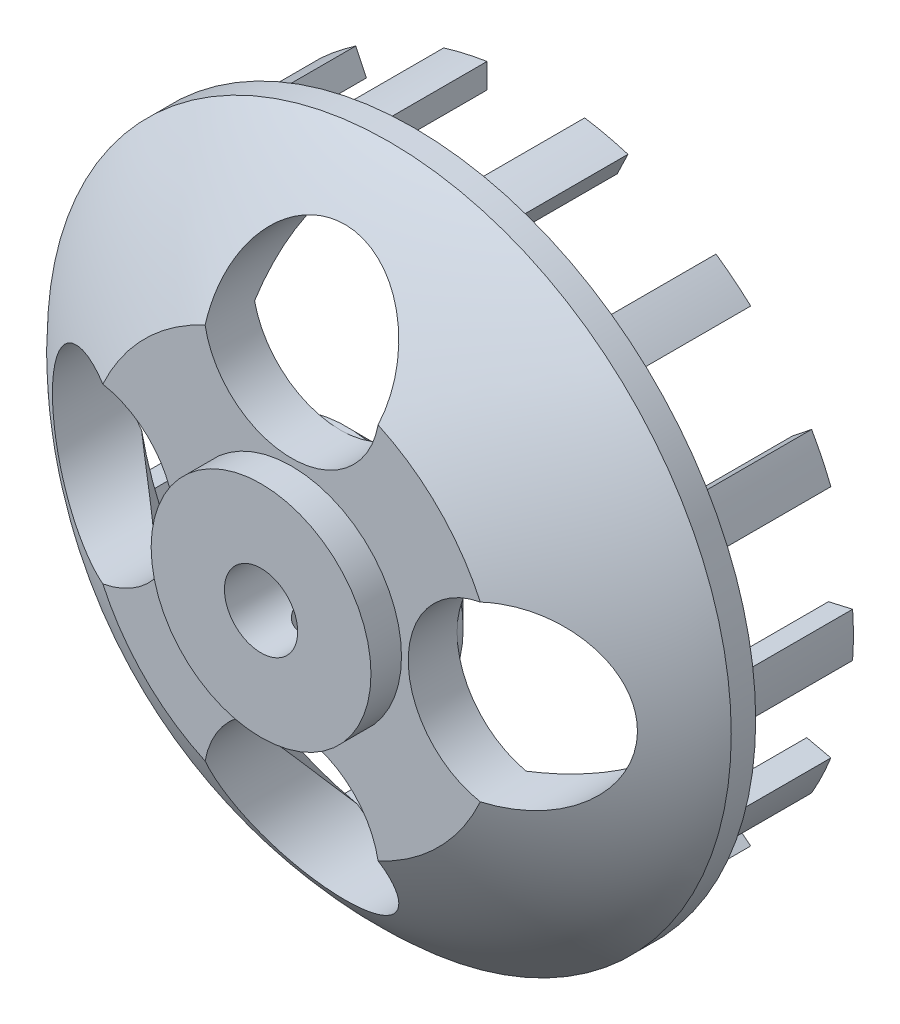
SolidWorks part; units mm, degrees
material "1060 Alloy"
ref_plane "Front Plane" through (0, 0, 0) normal (0, 0, 1) x (1, 0, 0)
ref_plane "Top Plane" through (0, 0, 0) normal (0, 1, 0) x (1, 0, 0)
ref_plane "Right Plane" through (0, 0, 0) normal (1, 0, 0) x (0, 0, -1)
sketch "Sketch1" plane through (0, 0, 0) normal (0, 0, 1) x (1, 0, 0)
  circle A0 centre (0, 0) radius 14
extrude "Boss-Extrude1" add sketch "Sketch1" along normal blind 22
sketch "Sketch2" plane through (0, 0, 0) normal (0, 0, -1) x (-1, 0, 0)
  circle A0 centre (0, 0) radius 12
extrude "Cut-Extrude1" cut sketch "Sketch2" against normal blind 15
sketch "Sketch3" plane through (0, 0, 0) normal (0, 0, -1) x (-1, 0, 0)
  circle A0 centre (0, 0) radius 13
  circle A1 centre (0, 0) radius 17.0368
extrude "Cut-Extrude2" cut sketch "Sketch3" against normal blind 15
sketch "Sketch4" plane through (0, 0, 0) normal (0, 0, -1) x (-1, 0, 0)
  circle A0 centre (0, 0) radius 15.1633
extrude "Cut-Extrude3" cut sketch "Sketch4" against normal blind 10
sketch "Sketch5" plane through (0, 0, 22) normal (0, 0, 1) x (1, 0, 0)
  circle A0 centre (0, 0) radius 4.5
  circle A1 centre (0, 0) radius 16.9949
extrude "Cut-Extrude4" cut sketch "Sketch5" against normal blind 2
sketch "Sketch6" plane through (0, 0, 20) normal (0, 0, 1) x (1, 0, 0)
  circle A0 centre (0, 0) radius 8.5
sketch "Sketch7" plane through (0, 0, 0) normal (0, 1, 0) x (1, 0, 0)
  line L1 (-8.5, -20) -> (8.5, -20) construction
  line L2 (-14, -15) -> (-14, -20) construction
  line L6 (-14, -16) -> (-16.2111, -22.8505)
  line L7 (-16.2111, -22.8505) -> (-8.5, -20)
  line L8 (0, -9.1425) -> (0, -24.4968) construction
  spline S1 degree 2 poles (-8.5, -20) (-12.3428, -17.8938) (-14, -16) knots 0 0 0 1 1 1
sketch "Sketch8" plane through (0, 0, 20) normal (0, 0, 1) x (1, 0, 0)
  circle A2 centre (0, 8.375) radius 3.6
extrude "Cut-Extrude5" cut sketch "Sketch8" against normal blind 7
pattern_circular "CirPattern1" count 4 every 90 about axis through (0, 0, 22) along (0, 0, -1) of "Cut-Extrude5"
revolve "Cut-Revolve2" cut sketch "Sketch7" angle 360 about L8
sketch "Sketch11" plane through (0, 0, 22) normal (0, 0, 1) x (1, 0, 0)
  circle A0 centre (0, 0) radius 5.62
extrude "Cut-Extrude6" cut sketch "Sketch11" against normal blind 0.75
sketch "Sketch12" plane through (0, 0, 21.25) normal (0, 0, 1) x (1, 0, 0)
  circle A0 centre (0, 0) radius 1.5
extrude "Cut-Extrude7" cut sketch "Sketch12" against normal blind 18
sketch "Sketch13" plane through (0, 0, 15) normal (0, 0, -1) x (-1, 0, 0)
  circle A0 centre (0, 0) radius 4.775
  circle A1 centre (0, 0) radius 8.375
extrude "Cut-Extrude8" cut sketch "Sketch13" against normal blind 3
fillet "Fillet1" radius 2.75 1 edges at (-4.775, 0, 15) profile chamfer
fillet "Fillet2" radius 3 4 edges at (5.922, 5.922, 15) (-5.922, -5.922, 15) (5.922, -5.922, 15) (-5.922, 5.922, 15) profile chamfer
sketch "Sketch14" plane through (0, 0, 10) normal (0, 0, -1) x (-1, 0, 0)
  line L0 (-2, 11.8322) -> (2, 11.8322)
  line L2 (2, 11.8322) -> (2, 16.0493)
  line L3 (2, 16.0493) -> (-2, 16.0493)
  line L4 (-2, 11.8322) -> (-2, 16.0493)
  circle A0 centre (0, 0) radius 12 construction
  point P0 (0, 0)
extrude "Cut-Extrude10" cut sketch "Sketch14" against normal blind 5
pattern_circular "CirPattern3" count 14 every 25.714 about axis through (0, 0, 15) along (0, 0, -1) of "Cut-Extrude10" reverse direction yes
sketch "Sketch16" plane through (0, 0, 0) normal (0, 1, 0) x (1, 0, 0)
  circle A0 centre (0, -18.9466) radius 0.75
  point P2 (0, -18.9466)
extrude "Cut-Extrude11" cut sketch "Sketch16" against normal blind 6
